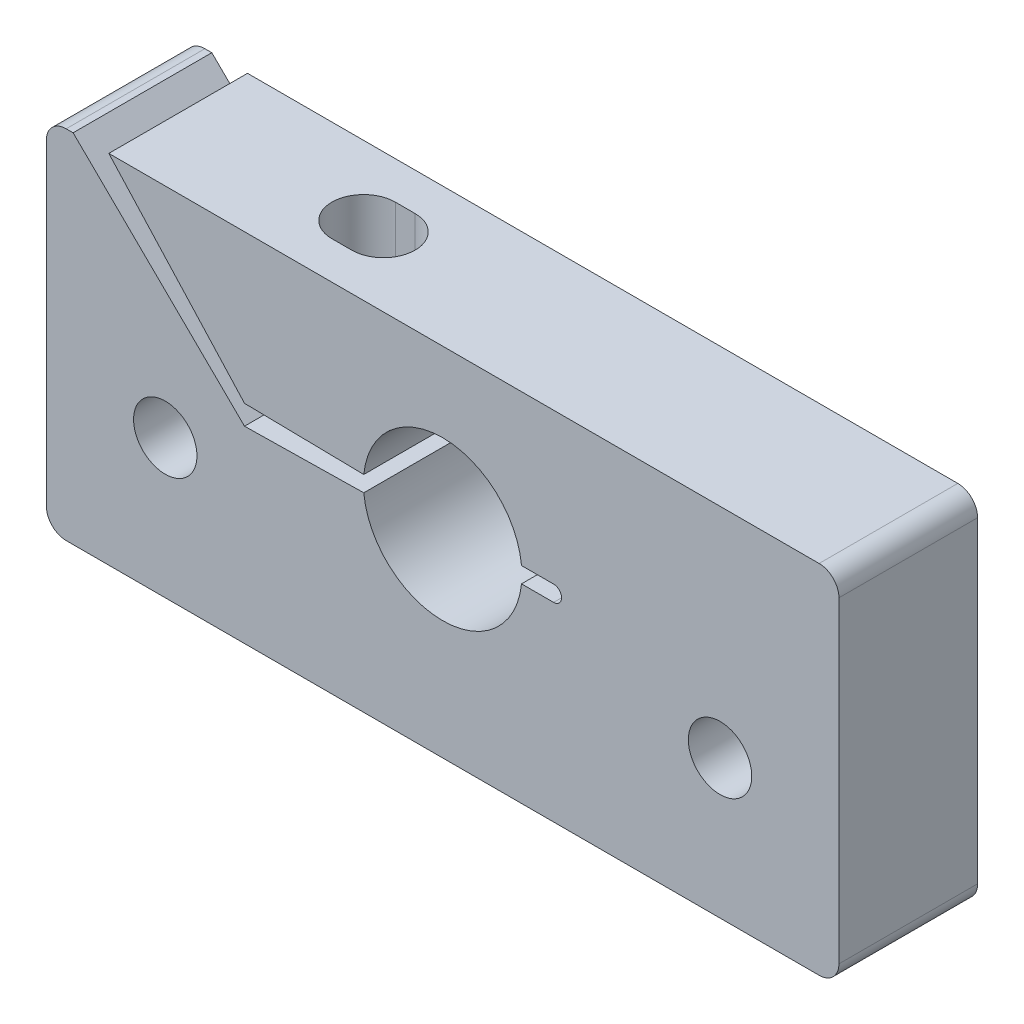
SolidWorks part; units mm, degrees
ref_plane "Front Plane" through (0, 0, 0) normal (0, 0, 1) x (1, 0, 0)
ref_plane "Top Plane" through (0, 0, 0) normal (0, 1, 0) x (1, 0, 0)
ref_plane "Right Plane" through (0, 0, 0) normal (1, 0, 0) x (0, 0, -1)
sketch "Sketch1" plane through (0, 0, 0) normal (0, 0, 1) x (1, 0, 0)
  line L0 (-43.3338, 0) -> (30.2546, 0) construction
  line L1 (-10, 0) -> (-19.1197, 9.4437) construction
  line L2 (-20, 8) -> (-18.6497, 8)
  line L3 (-20, 8) -> (-20, -10)
  line L4 (-20, -10) -> (20, -10)
  line L5 (20, 8) -> (20, -10)
  line L6 (-10, 0.5) -> (-3.9799, 0.4)
  line L7 (-10, 0.5) -> (-10, -0.5) construction
  line L8 (-10, -0.5) -> (-3.9799, -0.4)
  line L9 (6, 0.4) -> (6, -0.4)
  line L10 (-10, 0.5) -> (-16.8484, 8)
  line L11 (-10, -0.5) -> (-18.6497, 8)
  line L12 (3.9799, 0.4) -> (6, 0.4)
  line L13 (3.9799, -0.4) -> (6, -0.4)
  line L14 (-16.8484, 8) -> (20, 8)
  line L15 (0, 10.4655) -> (0, -11.9899) construction
  arc A0 (-3.9799, -0.4) -> (3.9799, -0.4) centre (0, 0) ccw
  arc A1 (3.9799, 0.4) -> (-3.9799, 0.4) centre (0, 0) ccw
  circle A2 centre (-14, -3) radius 2.2 construction
  circle A3 centre (-14, -3) radius 1.6
  circle A4 centre (14, -3) radius 1.6
  dimension "D1" = 8
  dimension "D2" = 4.4
  dimension "D5" = 20
  dimension "D7" = 2
  dimension "D16" = 3.2
  dimension "D3" = 8
  dimension "D6" = 0.8
  dimension "D8" = 46
  dimension "D9" = 6
  dimension "D10" = 1.5
  dimension "D11" = 1.6
  dimension "D12" = 40
  dimension "D14" = 0.8
  dimension "D15" = 1
  dimension "D17" = 28
  dimension "D18" = 3
  dimension "D19" = 10
extrude "Boss-Extrude1" add sketch "Sketch1" along normal blind 3.5 and the other way blind 3.5
sketch "Sketch3" plane through (0, -10, 0) normal (0, -1, 0) x (1, 0, 0)
  line L0 (-10, 3.5) -> (-3.9799, 3.5) construction
  line L1 (-20, 3.5) -> (20, 3.5) construction
  line L7 (-6.99, 2.7251) -> (-6.99, -2.5156) construction
  line L10 (20, -3.5) -> (20, 3.5) construction
  circle A0 centre (-6.99, 0) radius 2.2
  circle A1 centre (-6.99, 0) radius 1.6
  point P6 (-6.99, 3.5)
  dimension "D1" = 4.4
  dimension "D2" = 3.2
extrude "Cut-Extrude1" cut sketch "Sketch3" against normal up to next contours A1
extrude "Cut-Extrude2" cut sketch "Sketch3<3>" against normal blind 6
sketch "Sketch3<3>" plane through (0, -10, 0) normal (0, -1, 0) x (1, 0, 0) same geometry as "Sketch3"
sketch "Sketch4" plane through (0, 8, 0) normal (0, 1, 0) x (1, 0, 0)
  line L0 (-7.49, 0) -> (-6.49, 0) construction
  line L1 (-7.49, 1.6) -> (-6.49, 1.6)
  line L2 (-7.49, -1.6) -> (-6.49, -1.6)
  arc A0 (-7.49, 1.6) -> (-7.49, -1.6) centre (-7.49, 0) ccw
  arc A1 (-6.49, -1.6) -> (-6.49, 1.6) centre (-6.49, 0) ccw
  point P2 (-6.99, 0)
  dimension "D1" = 3.2
  dimension "D2" = 1
extrude "Cut-Extrude3" cut sketch "Sketch4" against normal up to next
fillet "Fillet1" radius 1 4 edges at (-20, -10, 0) (20, -10, 0) (20, 8, 0) (-20, 8, 0)
fillet "Fillet2" 2 edges at (6, 0.4, 0) (6, -0.4, 0) type full round first side face at (4.99, 0.4, 0) second side face at (4.99, -0.4, 0) middle face at (6, 0, 0)
